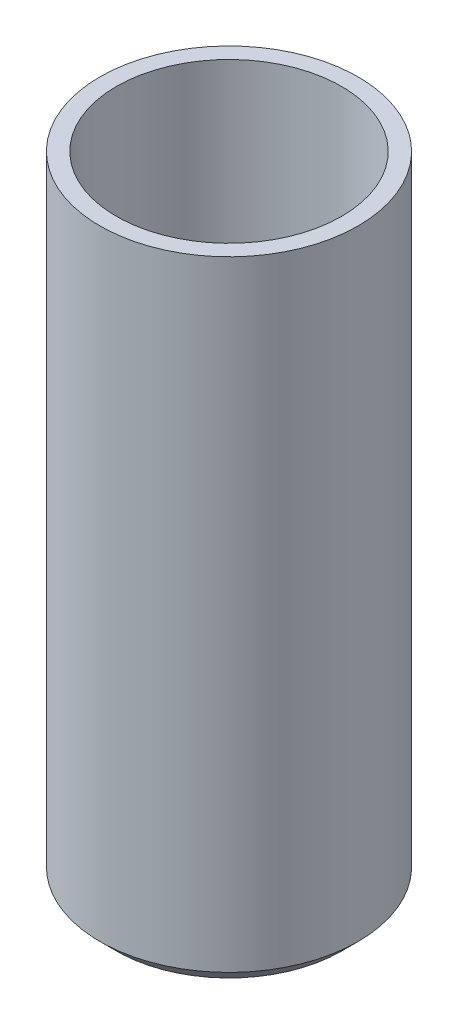
SolidWorks part; units mm, degrees
ref_plane "Front Plane" through (0, 0, 0) normal (0, 0, 1) x (1, 0, 0)
ref_plane "Top Plane" through (0, 0, 0) normal (0, 1, 0) x (1, 0, 0)
ref_plane "Right Plane" through (0, 0, 0) normal (1, 0, 0) x (0, 0, -1)
sketch "Sketch1" plane through (0, 0, 0) normal (0, 0, 1) x (1, 0, 0)
  line L0 (0, 0) -> (-5.1186, 0)
  line L1 (-5.45, 0.3314) -> (-5.45, 30)
  line L2 (-5.45, 30) -> (-6.25, 30)
  line L3 (-6.25, 30) -> (-6.25, 0)
  line L4 (-5.45, -0.8) -> (0, -0.8)
  line L5 (0, -0.8) -> (0, 0)
  line L6 (-5.45, -0.8) -> (-6.25, 0)
  line L7 (-5.45, 0.3314) -> (-5.1186, 0)
  line L8 (-5.45, 0) -> (-5.45, 0.3314) construction
  line L9 (-5.1186, 0) -> (-5.45, 0) construction
  line L10 (-6.25, 0) -> (-6.25, -0.8) construction
  line L11 (-6.25, -0.8) -> (-5.45, -0.8) construction
  line L12 (0, -549.9037) -> (0, 26945.2836) construction
  point P11 (-6.0773, -0.8)
  point P14 (0, 0)
  point P15 (0, 0)
  point P16 (0, 0)
  point P17 (-5.85, 30)
  dimension "D1" = 12.5
  dimension "D2" = 0.8
  dimension "D3" = 0.8
  dimension "D4" = 0.8
  dimension "D5" = 30
revolve "Revolve1" add sketch "Sketch1" angle 360 about L12
